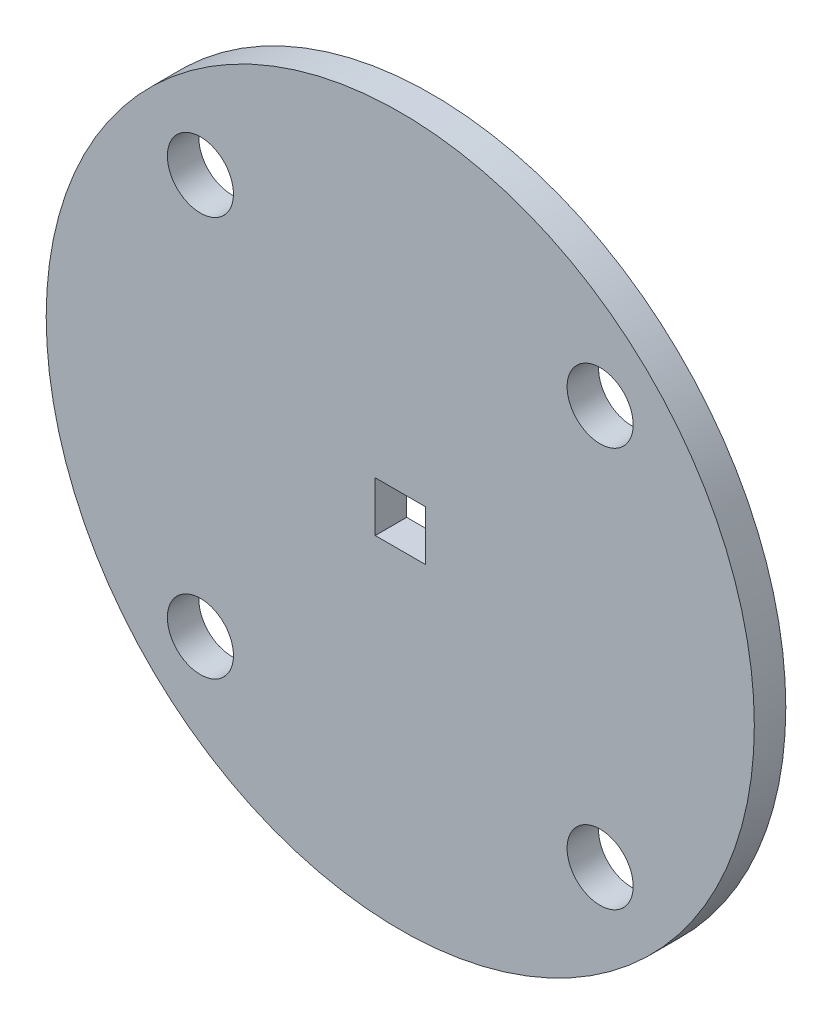
SolidWorks part; units mm, degrees
material "Plain Carbon Steel"
ref_plane "Front Plane" through (0, 0, 0) normal (0, 0, 1) x (1, 0, 0)
ref_plane "Top Plane" through (0, 0, 0) normal (0, 1, 0) x (1, 0, 0)
ref_plane "Right Plane" through (0, 0, 0) normal (1, 0, 0) x (0, 0, -1)
sketch "Sketch1" plane through (0, 0, 0) normal (0, 0, 1) x (1, 0, 0)
  circle A0 centre (0, 0) radius 24
  dimension "D1" = 48
base flange "Base-Flange1" sketch "Sketch1" thickness 2 reverse thickness direction no parameters "D1"=1.6
sketch "Sketch6" plane through (0, 0, 0) normal (0, 0, 1) x (1, 0, 0)
  line L5 (-1.59, -1.59) -> (1.59, -1.59)
  line L6 (-1.59, -1.59) -> (-1.59, 1.59)
  line L7 (-1.59, 1.59) -> (1.59, 1.59)
  line L8 (1.59, -1.59) -> (1.59, 1.59)
  line L9 (-1.59, -1.59) -> (1.59, 1.59) construction
  line L10 (-1.59, 1.59) -> (1.59, -1.59) construction
  circle A0 centre (-12.7, 12.7) radius 2.1
  circle A1 centre (12.7, 12.7) radius 2.1
  circle A2 centre (12.7, -12.7) radius 2.1
  circle A3 centre (-12.7, -12.7) radius 2.1
  point P0 (0, 0)
  point P1 (0, 0)
  dimension "D9" = 4.2
  dimension "D10" = 4.2
  dimension "D11" = 4.2
  dimension "D12" = 4.2
  dimension "D2" = 3.18
  dimension "D3" = 3.18
extrude "Cut-Extrude1" cut sketch "Sketch6" against normal blind 10 normal cut yes
sketch "Sketch8" plane through (0, 0, 0) normal (0, 0, 1) x (1, 0, 0)
  circle A0 centre (0, 0) radius 22.5
  circle A1 centre (0, 0) radius 24
  dimension "D1" = 45
extrude "Cut-Extrude3" cut sketch "Sketch8" against normal blind 10 normal cut yes
sketch "Bend-Lines1" [suppressed] plane through (0, 0, 0) normal (0, 1, 0) x (1, 0, 0)
sketch "Bounding-Box1" [suppressed] plane through (0, 0, 0) normal (0, 1, 0) x (1, 0, 0)
sheet metal parameters "Sheet-Metal8" thickness 2 parameters "D1"=1.6
flat pattern "Flat-Pattern8" [suppressed]
sketch "Bend-Lines2" plane through (0, 0, 0) normal (0, 1, 0) x (1, 0, 0)
sketch3d "Bounding-Box2" [suppressed]
  line L0 (23.9508, 24.049, 0) -> (-24.049, 23.9508, 0) construction
  line L1 (24.049, -23.9508, 0) -> (-23.9508, -24.049, 0) construction
  line L2 (23.9508, 24.049, 0) -> (24.049, -23.9508, 0) construction
  line L3 (-24.049, 23.9508, 0) -> (-23.9508, -24.049, 0) construction
sheet metal parameters "Sheet-Metal9" thickness 2 parameters "D1"=1.6
flat pattern "Flat-Pattern8"
sketch "Bend-Lines2" plane through (0, 0, 0) normal (0, 1, 0) x (1, 0, 0)
sketch3d "Bounding-Box2" [suppressed]
  line L0 (-23.9508, 24.049, 0) -> (24.049, 23.9508, 0) construction
  line L1 (-24.049, -23.9508, 0) -> (23.9508, -24.049, 0) construction
  line L2 (-23.9508, 24.049, 0) -> (-24.049, -23.9508, 0) construction
  line L3 (24.049, 23.9508, 0) -> (23.9508, -24.049, 0) construction
sheet metal parameters "Sheet-Metal11" thickness 2 parameters "D1"=1.6
flat pattern "Flat-Pattern8"
sketch "Bend-Lines2" plane through (0, 0, 0) normal (0, 1, 0) x (1, 0, 0)
sketch3d "Bounding-Box2" [suppressed]
  line L0 (-22.4787, -22.5213, 0) -> (22.5213, -22.4786, 0) construction
  line L1 (-22.5213, 22.4786, 0) -> (22.4786, 22.5213, 0) construction
  line L2 (-22.4787, -22.5213, 0) -> (-22.5213, 22.4786, 0) construction
  line L3 (22.5213, -22.4786, 0) -> (22.4786, 22.5213, 0) construction
